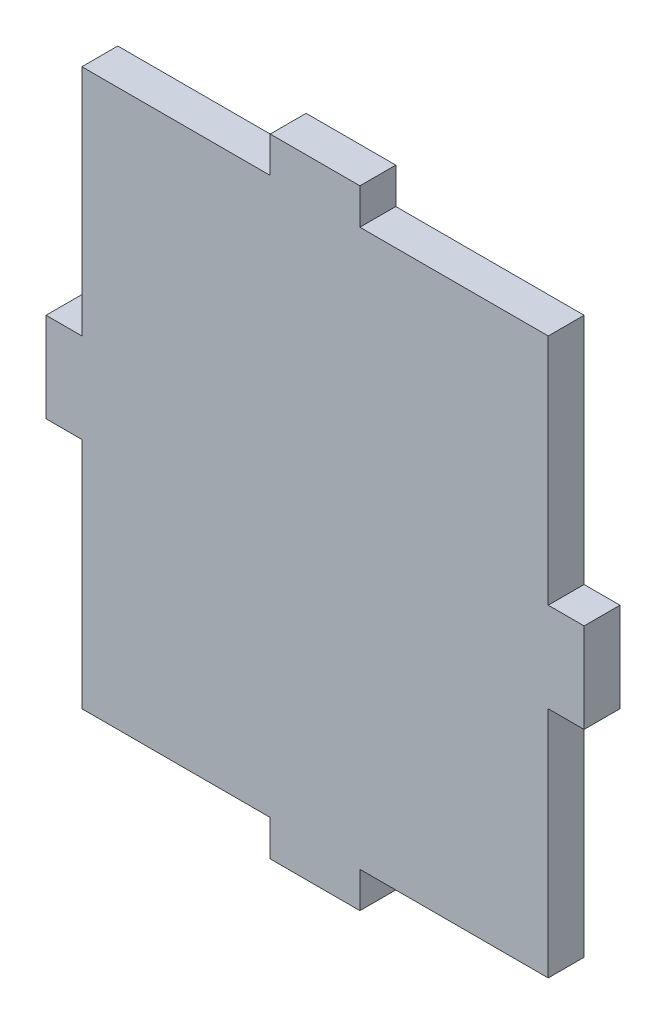
SolidWorks part; units mm, degrees
ref_plane "Front Plane" through (0, 0, 0) normal (0, 0, 1) x (1, 0, 0)
ref_plane "Top Plane" through (0, 0, 0) normal (0, 1, 0) x (1, 0, 0)
ref_plane "Right Plane" through (0, 0, 0) normal (1, 0, 0) x (0, 0, -1)
sketch "Sketch1" plane through (0, 0, 0) normal (0, 0, 1) x (1, 0, 0)
  line L1 (0, 0) -> (52, 0)
  line L2 (0, 0) -> (0, 62)
  line L3 (0, 62) -> (52, 62)
  line L4 (52, 0) -> (52, 62)
  dimension "D1" = 52
  dimension "D2" = 62
extrude "Boss-Extrude1" add sketch "Sketch1" along normal blind 4
sketch "Sketch2" plane through (0, 0, 4) normal (0, 0, 1) x (1, 0, 0)
  line L0 (0, 62) -> (0, 0) construction
  line L1 (0, 36) -> (-4, 36)
  line L2 (0, 36) -> (0, 26)
  line L3 (0, 26) -> (-4, 26)
  line L4 (-4, 36) -> (-4, 26)
  line L5 (52, 0) -> (52, 62) construction
  line L6 (52, 36) -> (56, 36)
  line L7 (52, 36) -> (52, 26)
  line L8 (52, 26) -> (56, 26)
  line L9 (56, 36) -> (56, 26)
  line L10 (0, 0) -> (52, 0) construction
  line L11 (21, 0) -> (31, 0)
  line L12 (21, 0) -> (21, -4)
  line L13 (21, -4) -> (31, -4)
  line L14 (31, 0) -> (31, -4)
  line L15 (52, 62) -> (0, 62) construction
  line L16 (21, 62) -> (31, 62)
  line L17 (21, 62) -> (21, 66)
  line L18 (21, 66) -> (31, 66)
  line L19 (31, 62) -> (31, 66)
  line L21 (26, 0) -> (26, 23.7889) construction
  dimension "D1" = 10
  dimension "D2" = 10
  dimension "D3" = 26
  dimension "D4" = 10
  dimension "D6" = 4
extrude "Boss-Extrude2" add sketch "Sketch2" against normal blind 4
